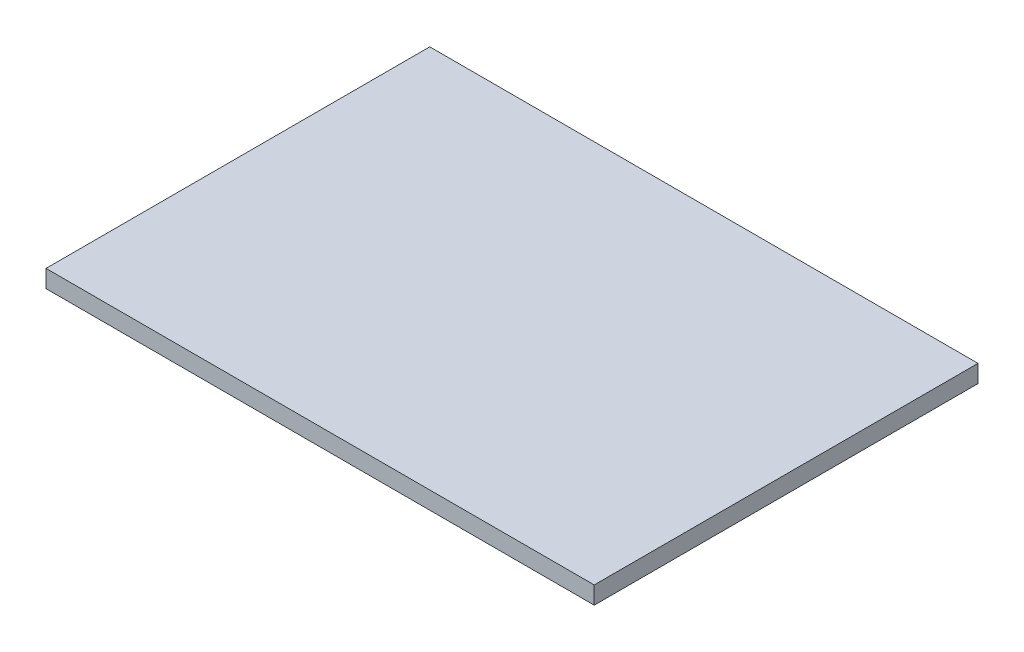
SolidWorks part; units mm, degrees
ref_plane "Front Plane" through (0, 0, 0) normal (0, 0, 1) x (1, 0, 0)
ref_plane "Top Plane" through (0, 0, 0) normal (0, 1, 0) x (1, 0, 0)
ref_plane "Right Plane" through (0, 0, 0) normal (1, 0, 0) x (0, 0, -1)
sketch "Sketch1" plane through (0, 0, 0) normal (0, 1, 0) x (1, 0, 0)
  line L1 (0, 0) -> (50, 0)
  line L2 (0, 0) -> (0, 35)
  line L3 (0, 35) -> (50, 35)
  line L4 (50, 0) -> (50, 35)
  dimension "D1" = 35
  dimension "D2" = 50
extrude "Boss-Extrude1" add sketch "Sketch1" along normal blind 1.6
